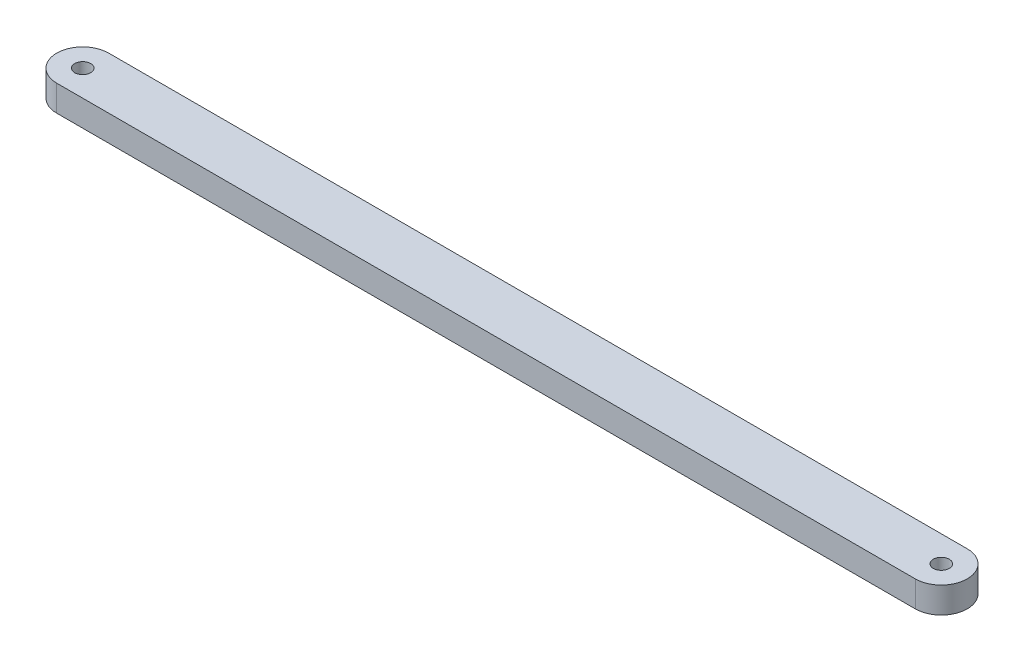
SolidWorks part; units mm, degrees
ref_plane "Front Plane" through (0, 0, 0) normal (0, 0, 1) x (1, 0, 0)
ref_plane "Top Plane" through (0, 0, 0) normal (0, 1, 0) x (1, 0, 0)
ref_plane "Right Plane" through (0, 0, 0) normal (1, 0, 0) x (0, 0, -1)
sketch "Sketch1" plane through (0, 0, 0) normal (0, 1, 0) x (1, 0, 0)
  line L0 (-165, 0) -> (165, 0) construction
  line L4 (-165, 10) -> (165, 10)
  line L5 (-165, -10) -> (165, -10)
  arc A3 (-165, 10) -> (-165, -10) centre (-165, 0) ccw
  arc A4 (165, -10) -> (165, 10) centre (165, 0) ccw
  circle A5 centre (-165, 0) radius 3.075
  circle A6 centre (165, 0) radius 3.075
  point P2 (0, 0)
  dimension "D3" = 6.15
  dimension "D4" = 6.15
  dimension "D1" = 20
  dimension "D2" = 330
extrude "Boss-Extrude1" add sketch "Sketch1" along normal blind 10
equation "\"D2@Sketch1\"=165+165"
